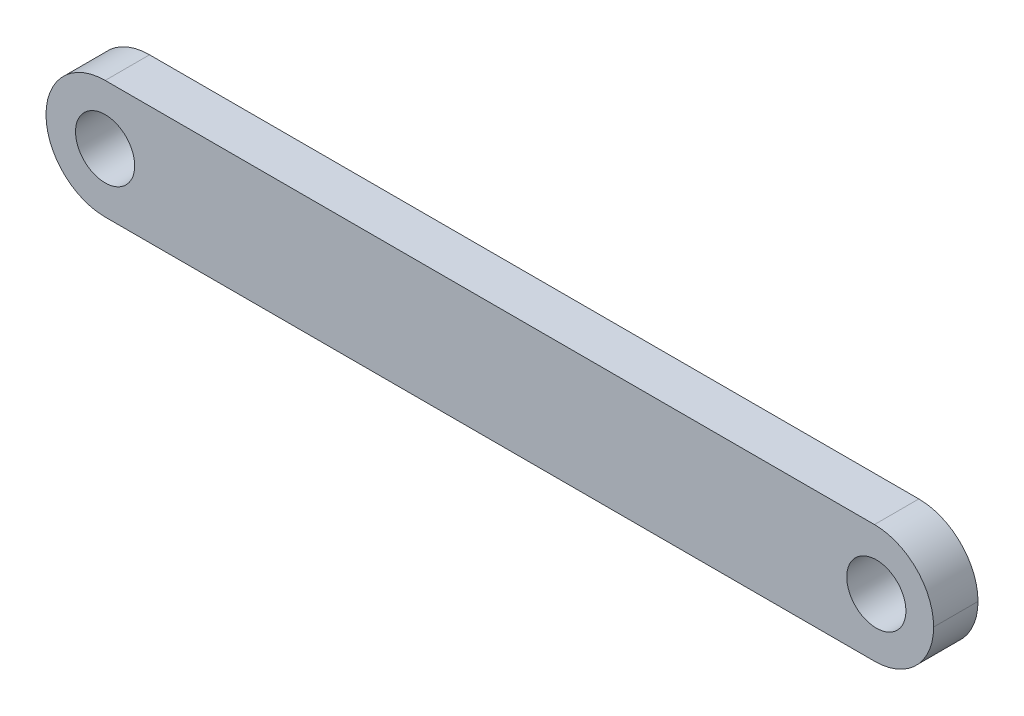
SolidWorks part; units mm, degrees
ref_plane "前视基准面" through (0, 0, 0) normal (0, 0, 1) x (1, 0, 0)
ref_plane "上视基准面" through (0, 0, 0) normal (0, 1, 0) x (1, 0, 0)
ref_plane "右视基准面" through (0, 0, 0) normal (1, 0, 0) x (0, 0, -1)
other "Configuration Table"
sketch "草图1" plane through (0, 0, 0) normal (0, 0, 1) x (1, 0, 0)
  line L0 (-30, 0) -> (0, 0) construction
  line L1 (-30, -4) -> (30, -4)
  line L2 (-30, -4) -> (-30, 4)
  line L3 (-30, 4) -> (30, 4)
  line L4 (30, -4) -> (30, 4)
  line L5 (-30, -4) -> (30, 4) construction
  line L6 (-30, 4) -> (30, -4) construction
  circle A1 centre (-26.0051, 0) radius 2
  circle A2 centre (26.1277, 0) radius 2
  point P0 (0, 0)
  dimension "D1" = 60
  dimension "D2" = 8
extrude "凸台-拉伸1" add sketch "草图1" along normal blind 3
fillet "圆角2" radius 4 4 edges at (30, -4, 1.5) (30, 4, 1.5) (-30, -4, 1.5) (-30, 4, 1.5)
